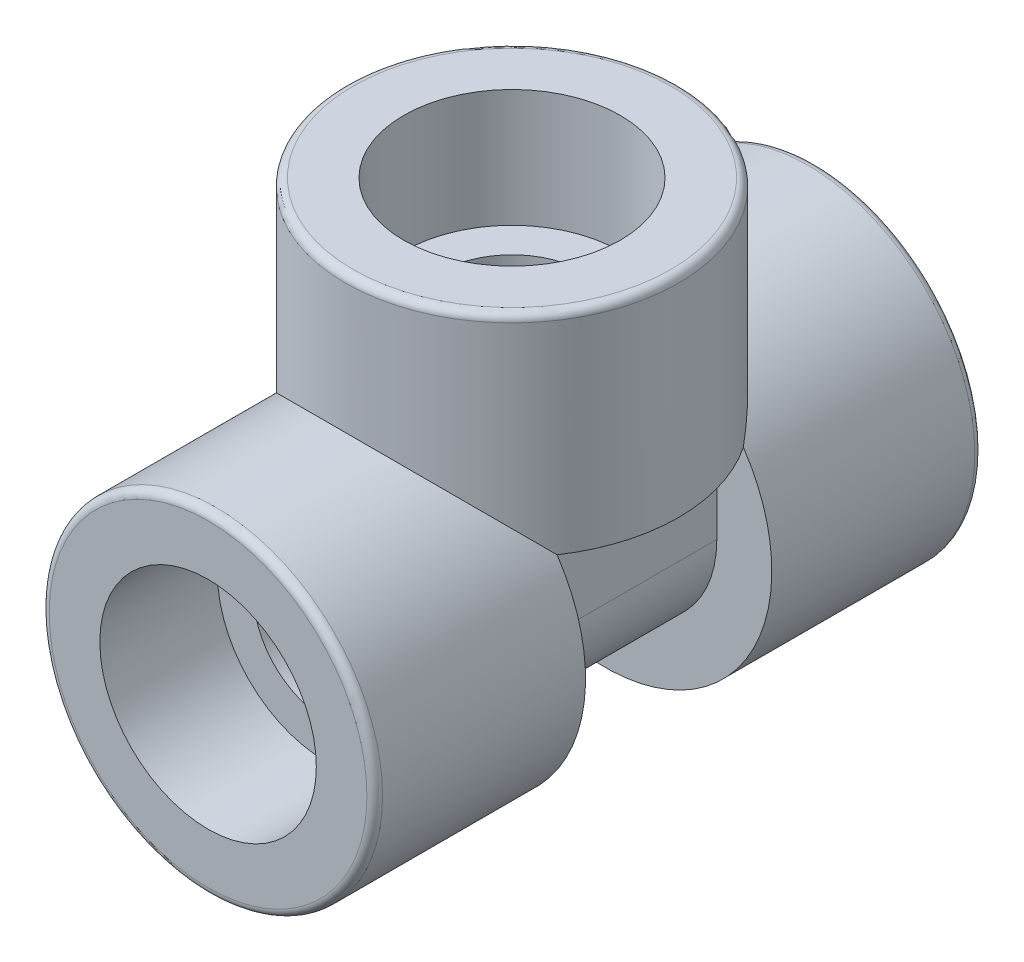
SolidWorks part; units mm, degrees
ref_plane "Front" through (0, 0, 0) normal (0, 0, 1) x (1, 0, 0)
ref_plane "Top" through (0, 0, 0) normal (0, 1, 0) x (1, 0, 0)
ref_plane "Right" through (0, 0, 0) normal (1, 0, 0) x (0, 0, -1)
sketch "Sketch1" plane through (0, 0, 0) normal (1, 0, 0) x (0, 0, -1)
  line L0 (15.0813, 5.842) -> (-15.0813, 5.842) construction
  line L1 (-15.0813, 5.842) -> (-15.0813, 8.763) construction
  line L2 (-15.0813, 8.763) -> (-24.6063, 8.763) construction
  line L3 (-24.6063, 8.763) -> (-24.6063, 13.4937)
  line L4 (-24.6063, 13.4937) -> (-7.5406, 13.4937)
  line L5 (-7.5406, 13.4937) -> (-7.5406, 9.042)
  line L6 (-7.5406, 9.042) -> (7.5406, 9.042)
  line L7 (7.5406, 9.042) -> (7.5406, 13.4937)
  line L8 (7.5406, 13.4937) -> (24.6063, 13.4937)
  line L9 (24.6063, 13.4937) -> (24.6063, 8.763)
  line L10 (24.6063, 8.763) -> (15.0813, 8.763) construction
  line L11 (15.0813, 8.763) -> (15.0813, 5.842) construction
  line L12 (24.6062, 0) -> (-24.6062, 0) construction
  line L13 (0, 0) -> (0, 5.842) construction
  line L14 (0, 5.842) -> (0, 9.042) construction
  line L15 (-24.6063, 8.763) -> (-24.6063, -8.763) construction
  line L16 (-15.0813, 5.842) -> (-15.0813, -5.842) construction
  line L17 (-24.6063, 8.763) -> (-24.6062, 0)
  line L18 (-24.6062, 0) -> (24.6062, 0)
  line L19 (24.6062, 0) -> (24.6063, 8.763)
  line L20 (-24.6063, 13.4937) -> (-24.6063, -13.4938) construction
  line L21 (-7.5406, 7.5406) -> (7.5406, 7.5406) construction
  line L22 (-7.5406, 7.5406) -> (-7.5406, -7.5406) construction
  line L23 (-7.5406, -7.5406) -> (7.5406, -7.5406) construction
  line L24 (7.5406, 7.5406) -> (7.5406, -7.5406) construction
  point P17 (-15.0813, 0)
  point P25 (0, 7.5406)
  point P26 (-7.5406, 0)
  dimension "Thickness" = 3.2
  dimension "D1" = 7.5406
revolve "Revolve1" add sketch "Sketch1" angle 360 about L12
sketch "Sketch2" plane through (0, 0, 0) normal (1, 0, 0) x (0, 0, -1)
  line L0 (5.842, 0) -> (5.842, 15.0813) construction
  line L1 (24.6062, 0) -> (-24.6062, 0) construction
  line L2 (5.842, 15.0813) -> (8.763, 15.0813) construction
  line L3 (8.763, 15.0813) -> (8.763, 24.6063) construction
  line L4 (8.763, 24.6063) -> (13.4937, 24.6063)
  line L5 (13.4937, 24.6063) -> (13.4938, 7.5406)
  line L6 (13.4938, 7.5406) -> (9.042, 7.5406)
  line L7 (9.042, 7.5406) -> (9.042, 0)
  line L8 (9.042, 0) -> (5.842, 0)
  line L9 (5.842, 0) -> (-5.842, 0) construction
  line L10 (8.763, 15.0813) -> (-8.763, 15.0813) construction
  line L11 (0, 9.042) -> (0, 15.0813) construction
  line L12 (5.842, 0) -> (0, 0)
  line L13 (0, 0) -> (0, 24.6063)
  line L14 (0, 24.6063) -> (8.763, 24.6063)
  line L15 (-7.5406, 7.5406) -> (7.5406, 7.5406) construction
  dimension "D1" = 17.526
  dimension "D2" = 11.684
  dimension "D3" = 4.7308
  dimension "D5" = 15.0813
  dimension "D6" = 9.525
  dimension "D7" = 3.2
revolve "Revolve2" add sketch "Sketch2" angle 360 about L13
sketch "Sketch5" plane through (0, 0, 7.5406) normal (0, 0, -1) x (-1, 0, 0)
  line L0 (9.042, 0) -> (-9.042, 0) construction
  line L1 (9.042, 0) -> (9.042, 7.5406)
  line L3 (-11.1902, 7.5406) -> (-4.9897, 7.5406) construction
  line L6 (9.042, 7.5406) -> (-9.042, 7.5406)
  line L7 (-9.042, 7.5406) -> (-9.042, 0)
  arc A0 (-9.042, 0) -> (9.042, 0) centre (0, 0) ccw
  circle A2 centre (0, 0) radius 9.042 construction
extrude "Extrude1" add sketch "Sketch5" along normal up to surface (15.0813 mm away) up to face at (0, -1.8636, -7.5406)
sketch "Sketch3" plane through (0, 0, 0) normal (1, 0, 0) x (0, 0, -1)
  line L0 (-24.6063, 8.763) -> (-15.0813, 8.763)
  line L1 (-15.0813, 8.763) -> (-15.0813, 5.842)
  line L2 (-15.0813, 5.842) -> (15.0813, 5.842)
  line L3 (15.0813, 5.842) -> (15.0813, 8.763)
  line L4 (15.0813, 8.763) -> (24.6063, 8.763)
  line L5 (24.6063, 8.763) -> (24.6062, 0)
  line L6 (24.6062, 0) -> (-24.6062, 0)
  line L7 (-24.6062, 0) -> (-24.6063, 8.763)
revolve "Cut-Revolve1" cut sketch "Sketch3" angle 360 about L6
sketch "Sketch4" plane through (0, 0, 0) normal (1, 0, 0) x (0, 0, -1)
  line L0 (0, 24.6063) -> (8.763, 24.6063)
  line L1 (8.763, 24.6063) -> (8.763, 15.0813)
  line L2 (8.763, 15.0813) -> (5.842, 15.0813)
  line L3 (5.842, 15.0813) -> (5.842, 0)
  line L4 (5.842, 0) -> (0, 0)
  line L5 (0, 0) -> (0, 24.6063)
revolve "Cut-Revolve2" cut sketch "Sketch4" angle 360 about L5
fillet "Fillet1" radius 0.635 3 edges at (-13.4937, 0, -24.6063) (0, 24.6063, -13.4937) (-13.4937, 0, 24.6063)
fillet "Fillet2" radius 6.35 2 edges at (0, 5.842, 5.842) (0, 5.842, -5.842)
equation "\"D1@Sketch2\" = \"Bore Dia@Sketch1\""
equation "\"D2@Sketch2\" = \"ID@Sketch1\""
equation "\"D3@Sketch2\" = \"D2@Sketch1\""
equation "\"D5@Sketch2\" = \"E@Sketch1\""
equation "\"D6@Sketch2\" = \"Bore Dp@Sketch1\""
equation "\"D7@Sketch2\" = \"Thickness@Sketch1\""
equation "\"D1@Sketch1\" = \"E@Sketch1\"/2"
